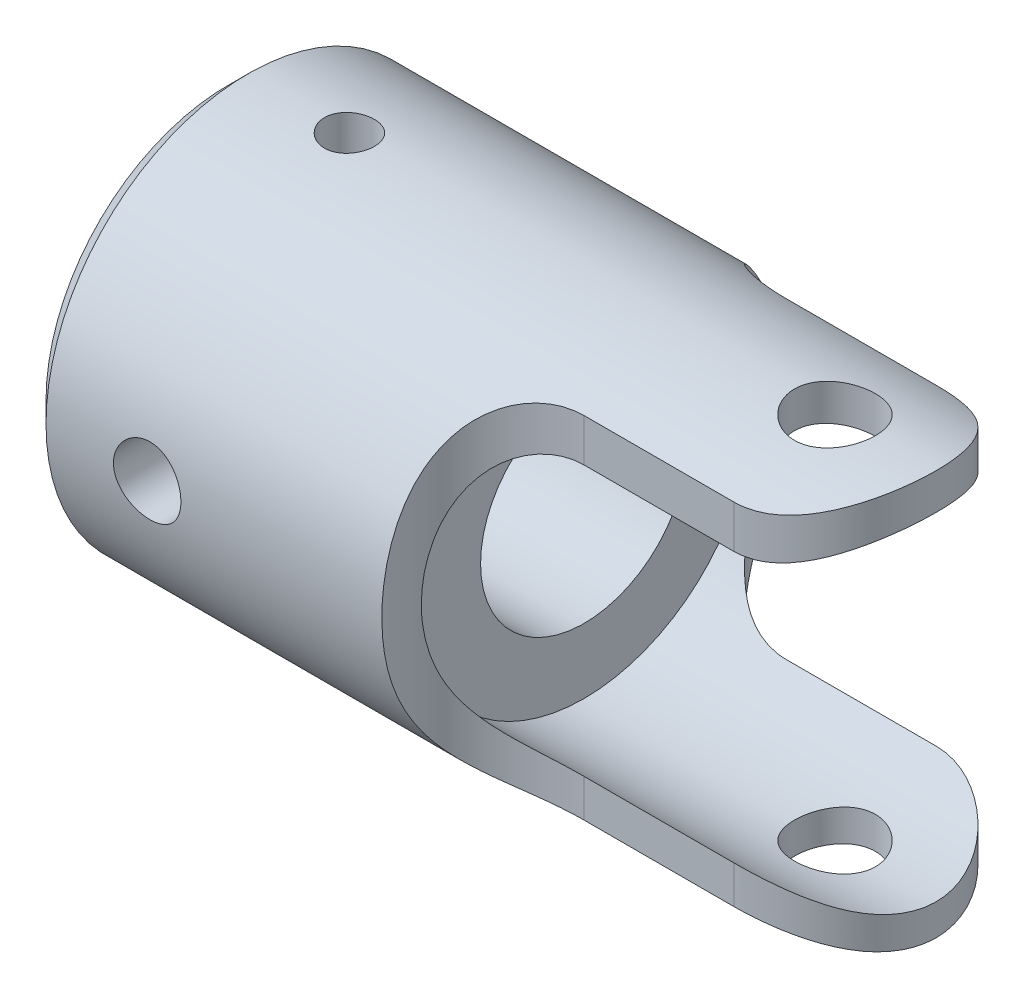
SolidWorks part; units mm, degrees
material "Alloy Steel"
ref_plane "Front Plane" through (0, 0, 0) normal (0, 0, 1) x (1, 0, 0)
ref_plane "Top Plane" through (0, 0, 0) normal (0, 1, 0) x (1, 0, 0)
ref_plane "Right Plane" through (0, 0, 0) normal (1, 0, 0) x (0, 0, -1)
ref_plane "Plane1" through (0, 0, 0) normal (0, 0, 1) x (1, 0, 0)
sketch "Sketch1" plane through (0, 0, 0) normal (0, 0, 1) x (1, 0, 0)
  line L0 (-19.05, 0) -> (-19.05, 5.7155)
  line L1 (-19.05, 5.7155) -> (-18.4155, 6.35)
  line L2 (-18.4155, 6.35) -> (12.7, 6.35)
  line L3 (12.7, 6.35) -> (12.7, 0)
  line L4 (12.7, 0) -> (-19.05, 0)
  line L5 (12.7, 0) -> (-19.05, 0) construction
revolve "Revolve1" add sketch "Sketch1" angle 360 about L5 reverse direction yes
ref_plane "Plane2" through (0, 0, 0) normal (0, 0, 1) x (1, 0, 0)
sketch "Sketch2" plane through (0, 0, 0) normal (0, 0, 1) x (1, 0, 0)
  line L0 (-15.24, 6.35) -> (-14.4565, 6.35)
  line L1 (-14.4565, 6.35) -> (-14.4565, 2.9907)
  line L2 (-14.4565, 2.9907) -> (-15.24, 2.9907)
  line L3 (-15.24, 2.9907) -> (-15.24, 6.35)
  line L4 (-15.24, 2.9907) -> (-15.24, 6.35) construction
revolve "Cut-Revolve1" cut sketch "Sketch2" angle 360 about L4 reverse direction yes
ref_plane "Plane3" through (0, 0, 0) normal (0, 1, 0) x (1, 0, 0)
sketch "Sketch3" plane through (0, 0, 0) normal (0, 1, 0) x (1, 0, 0)
  line L0 (-15.24, -4.1502) -> (-14.1817, -4.7612)
  line L1 (-14.1817, -4.7612) -> (-14.1817, -11.1061)
  line L2 (-14.1817, -11.1061) -> (-15.24, -11.1061)
  line L3 (-15.24, -11.1061) -> (-15.24, -4.1502)
  line L4 (-15.24, -11.1061) -> (-15.24, -4.1502) construction
revolve "Cut-Revolve2" cut sketch "Sketch3" angle 360 about L4 reverse direction yes
ref_plane "Plane4" through (0, 0, 0) normal (0, 1, 0) x (1, 0, 0)
sketch "Sketch4" plane through (0, 0, 0) normal (0, 1, 0) x (1, 0, 0)
  line L0 (-7.874, -15.875) -> (25.4, -15.875)
  line L1 (25.4, -15.875) -> (25.4, 15.875)
  line L2 (25.4, 15.875) -> (-7.874, 15.875)
  line L3 (-7.874, 15.875) -> (-7.874, 6.35)
  line L4 (-4.699, 3.175) -> (0, 3.175)
  line L5 (0, -3.175) -> (-4.699, -3.175)
  line L6 (-7.874, -6.35) -> (-7.874, -15.875)
  arc A0 (-7.874, 6.35) -> (-4.699, 3.175) centre (-4.699, 6.35) ccw
  arc A1 (0, 3.175) -> (0, -3.175) centre (0, 0) cw
  arc A2 (-4.699, -3.175) -> (-7.874, -6.35) centre (-4.699, -6.35) ccw
extrude "Cut-Extrude1" cut sketch "Sketch4" against normal blind 6.6842 and the other way blind 6.6842
ref_plane "Plane5" through (0, 0, 0) normal (0, 0, 1) x (1, 0, 0)
sketch "Sketch5" plane through (0, 0, 0) normal (0, 0, 1) x (1, 0, 0)
  line L0 (-19.0754, -0.0775) -> (-19.0754, 3.1725)
  line L1 (-19.0754, 3.1725) -> (-7.874, 3.1725)
  line L2 (-7.874, 3.1725) -> (-7.874, 5.2141)
  line L3 (-7.874, 5.2141) -> (12.6746, 5.2141)
  line L4 (12.6746, 5.2141) -> (12.6746, -0.0775)
  line L5 (12.6746, -0.0775) -> (-19.0754, -0.0775)
  line L6 (12.6746, -0.0775) -> (-19.0754, -0.0775) construction
  dimension "D1" = 5.2917
  dimension "D2" = 3.25
revolve "Cut-Revolve3" cut sketch "Sketch5" angle 360 about L6 reverse direction yes
ref_plane "Plane6" through (0, 0, 0) normal (0, 1, 0) x (1, 0, 0)
sketch "Sketch6" plane through (0, 0, 0) normal (0, 1, 0) x (1, 0, 0)
  circle A0 centre (0, 0) radius 1.27
extrude "Cut-Extrude2" cut sketch "Sketch6" against normal blind 6.6842 and the other way blind 6.6842
sketch "Sketch7" plane through (0, 0, 0) normal (0, 0, 1) x (1, 0, 0)
  point P0 (0, 0)
